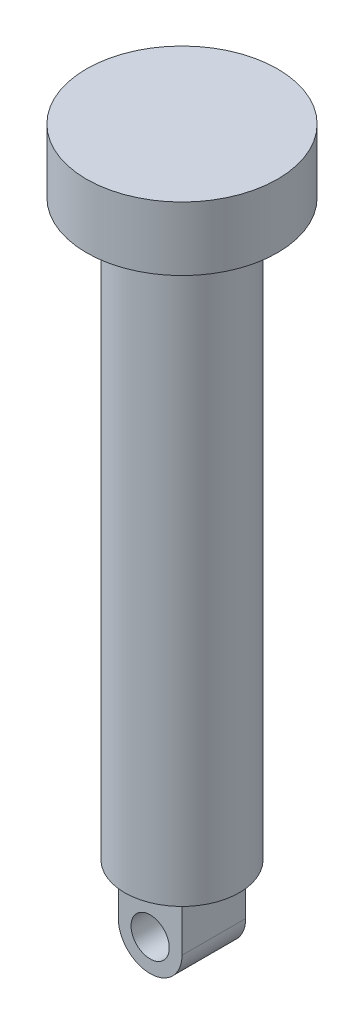
SolidWorks part; units mm, degrees
material "Chrome Stainless Steel"
ref_plane "Front Plane" through (0, 0, 0) normal (0, 0, 1) x (1, 0, 0)
ref_plane "Top Plane" through (0, 0, 0) normal (0, 1, 0) x (1, 0, 0)
ref_plane "Right Plane" through (0, 0, 0) normal (1, 0, 0) x (0, 0, -1)
sketch "Sketch1" plane through (0, 0, 0) normal (0, 1, 0) x (1, 0, 0)
  circle A0 centre (0, 0) radius 15
  circle A1 centre (0, 0) radius 9
  dimension "D1" = 30
  dimension "D2" = 18
extrude "Boss-Extrude1" add sketch "Sketch1" along normal blind 10 contours A1 | A0 A1 region at (-14.5757, 0, 0) region at (0, 0, 0)
extrude "Boss-Extrude2" add sketch "Sketch1<3>" against normal blind 90 contours A1 region at (0, 0, 0)
sketch "Sketch1<3>" plane through (0, 0, 0) normal (0, 1, 0) x (1, 0, 0) same geometry as "Sketch1"
sketch "Sketch2" plane through (0, 0, 0) normal (0, 0, 1) x (1, 0, 0)
  line L0 (0, -90) -> (0, -98) construction
  line L1 (-9, -90) -> (9, -90) construction
  line L2 (-5, -90) -> (-5, -98)
  line L3 (5, -98) -> (5, -90)
  line L4 (-5, -90) -> (5, -90)
  arc A0 (-5, -98) -> (5, -98) centre (0, -98) ccw
  circle A1 centre (0, -98) radius 3
  dimension "D1" = 6
  dimension "D3" = 5
  dimension "D2" = 8
extrude "Boss-Extrude3" add sketch "Sketch2" along normal mid plane 10
